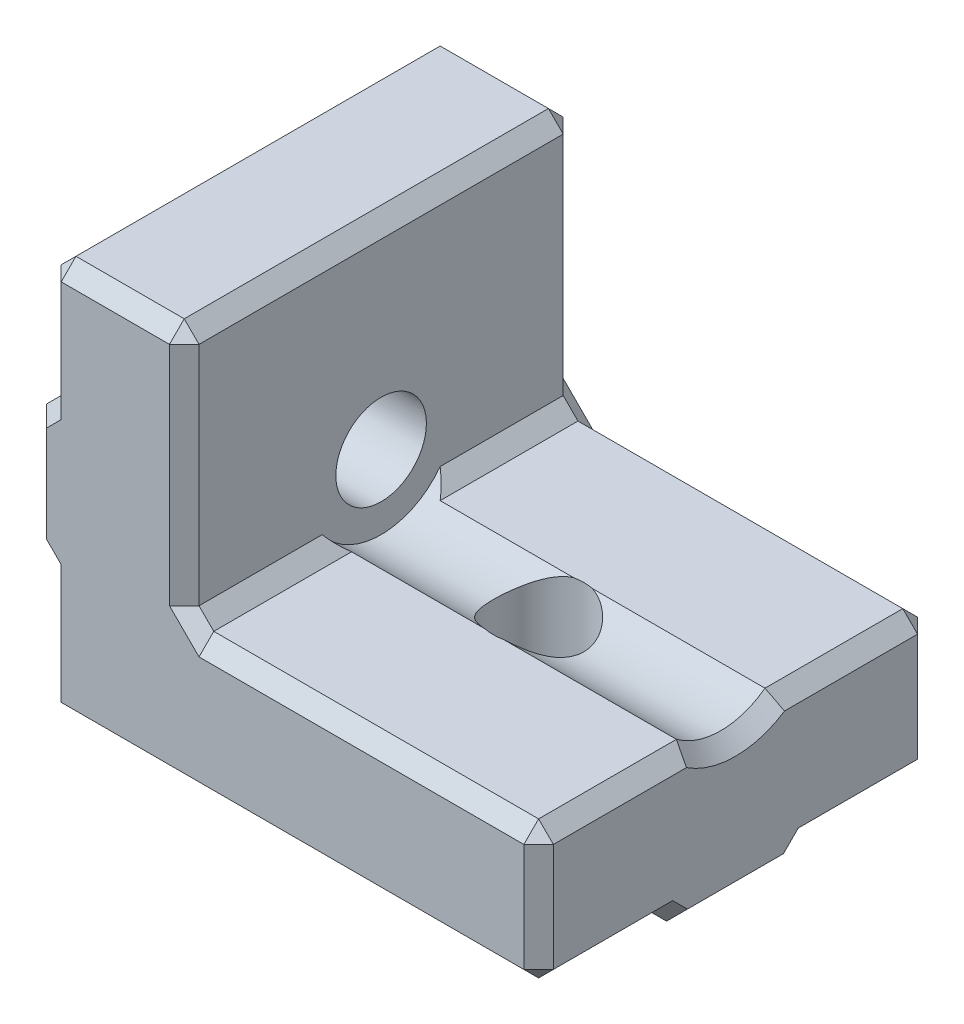
SolidWorks part; units mm, degrees
ref_plane "Front" through (0, 0, 0) normal (0, 0, 1) x (1, 0, 0)
ref_plane "Top" through (0, 0, 0) normal (0, 1, 0) x (1, 0, 0)
ref_plane "Right" through (0, 0, 0) normal (1, 0, 0) x (0, 0, -1)
sketch "Skizze1" plane through (0, 0, 0) normal (0, 0, 1) x (1, 0, 0)
  line L0 (0, 0) -> (0, 20)
  line L1 (0, 0) -> (25, 0)
  line L2 (25, 0) -> (25, 7)
  line L3 (25, 7) -> (7, 7)
  line L4 (7, 7) -> (7, 20)
  line L5 (7, 20) -> (0, 20)
  dimension "D1" = 25
  dimension "D2" = 7
  dimension "D3" = 7
  dimension "D4" = 20
extrude "Aufsatz-Linear austragen1" add sketch "Skizze1" along normal blind 20
sketch "Skizze5" plane through (0, 0, 0) normal (0, 0, -1) x (-1, 0, 0)
  line L0 (0, 10) -> (6.0519, 10) construction
  line L1 (0, 20) -> (0, 0) construction
  line L2 (0, 6.5) -> (0, 13.5)
  line L3 (0, 13.5) -> (0.75, 12.75)
  line L4 (0.75, 12.75) -> (0.75, 7.25)
  line L5 (0, 6.5) -> (0.75, 7.25)
  point P8 (0.75, 10)
  dimension "D1" = 7
  dimension "D2" = 0.75
  dimension "D3" = 45
extrude "Aufsatz-Linear austragen2" add sketch "Skizze5" against normal blind 20
sketch "Skizze6" plane through (0, 0, 0) normal (-1, 0, 0) x (0, 0, 1)
  line L0 (10, 0) -> (10, -8.6062) construction
  line L1 (20, 0) -> (0, 0) construction
  line L2 (6.5, 0) -> (13.5, 0)
  line L3 (13.5, 0) -> (12.75, -0.75)
  line L4 (12.75, -0.75) -> (7.25, -0.75)
  line L5 (6.5, 0) -> (7.25, -0.75)
  point P4 (13.0099, -0.75)
  point P9 (10, -0.75)
  dimension "D1" = 0.75
  dimension "D2" = 7
  dimension "D3" = 45
extrude "Aufsatz-Linear austragen3" add sketch "Skizze6" against normal up to surface (25 mm away) up to face at (25, 3.5, 10)
sketch "Skizze2" plane through (0, 0, 0) normal (-1, 0, 0) x (0, 0, 1)
  line L0 (10, 20) -> (10, 0) construction
  line L1 (20, 20) -> (0, 20) construction
  line L4 (6.5, 0) -> (0, 0) construction
  circle A0 centre (10, 10) radius 2.3
  point P4 (10, -0.75)
  point P5 (10, 0)
  point P8 (0, 0)
  point P9 (10, 10.0624)
  point P10 (0, 0)
  point P11 (0, 0)
  dimension "D1" = 4.6
extrude "Schnitt-Linear austragen1" cut sketch "Skizze2" against normal blind 20 and the other way blind 20
sketch "Skizze3" plane through (7, 0, 0) normal (1, 0, 0) x (0, 0, -1)
  circle A0 centre (-10, 10) radius 3.75
  point P2 (-10, 10)
  dimension "D1" = 7.5
extrude "Schnitt-Linear austragen2" cut sketch "Skizze3" along normal through all
sketch "Skizze4" plane through (0, 7, 0) normal (0, 1, 0) x (1, 0, 0)
  line L0 (15, 0) -> (15, -20) construction
  line L1 (25, 0) -> (7, 0) construction
  line L2 (25, -20) -> (7, -20) construction
  line L3 (7, -12.25) -> (7, -7.75) construction
  circle A0 centre (15, -10) radius 2.3
  dimension "D1" = 4.6
  dimension "D2" = 8
extrude "Schnitt-Linear austragen3" cut sketch "Skizze4" against normal blind 20
chamfer "Fase1" distance 0.75 angle 45 32 edges at (25, 7, 3.875) (25, 0, 16.75) (25, 0, 3.25) (25, 6.25, 10) (25, 7, 16.125) (7, 20, 10) (25, 3.5, 0) (16, 7, 0) (7, 7, 3.875) (7, 13.5, 0) (3.5, 20, 0) (12.5, 0, 0) (0, 3.25, 0) (0, 16.75, 0) (0, 20, 10) (0, 16.75, 20) (0, 3.25, 20) (3.5, 20, 20) (7, 13.5, 20) (12.5, 0, 20) (25, 3.5, 20) (16, 7, 20) (7, 7, 16.125) (-0.375, 6.875, 0) (-0.75, 10, 0) (-0.375, 13.125, 0) (-0.375, 6.875, 20) (-0.75, 10, 20) (-0.375, 13.125, 20) (25, -0.375, 6.875) (25, -0.75, 10) (25, -0.375, 13.125)
fillet "Verrundung1" radius 2 5 edges at (0, 0, 3.625) (0, 0, 16.375) (0, -0.375, 13.125) (0, -0.375, 6.875) (0, -0.75, 10)
sketch "Skizze7" plane through (0, 0, 0) normal (-1, 0, 0) x (0, 0, 1)
  circle A0 centre (10, 10) radius 4.15
  dimension "D1" = 8.3
extrude "Schnitt-Linear austragen4" cut sketch "Skizze7" along normal blind 20
sketch "Skizze8" plane through (0, 0, 0) normal (0, -1, 0) x (1, 0, 0)
  circle A0 centre (15, 10) radius 4.15
  dimension "D1" = 8.3
extrude "Schnitt-Linear austragen5" cut sketch "Skizze8" along normal blind 20
fillet "Verrundung2" radius 1 4 edges at (10.85, -0.75, 10) (19.15, -0.75, 10) (-0.75, 10, 14.15) (-0.75, 10, 5.85)
